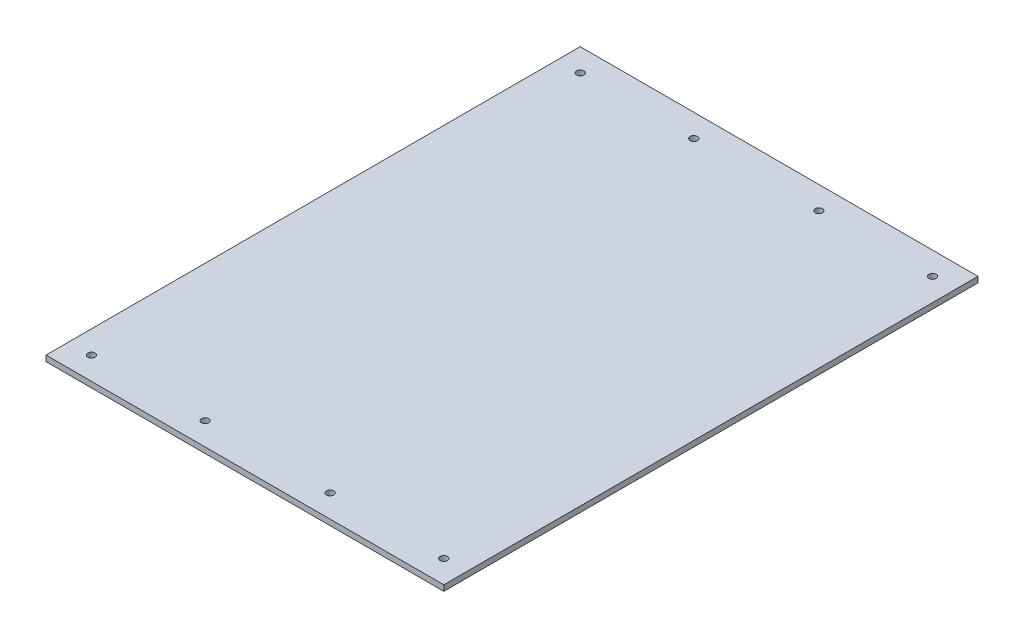
SolidWorks part; units mm, degrees
ref_plane "Front Plane" through (0, 0, 0) normal (0, 0, 1) x (1, 0, 0)
ref_plane "Top Plane" through (0, 0, 0) normal (0, 1, 0) x (1, 0, 0)
ref_plane "Right Plane" through (0, 0, 0) normal (1, 0, 0) x (0, 0, -1)
sketch "Sketch1" plane through (0, 0, 0) normal (0, 1, 0) x (1, 0, 0)
  line L1 (-175, -235) -> (175, -235)
  line L2 (-175, -235) -> (-175, 235)
  line L3 (-175, 235) -> (175, 235)
  line L4 (175, -235) -> (175, 235)
  line L5 (-175, -235) -> (175, 235) construction
  line L6 (-175, 235) -> (175, -235) construction
  point P0 (0, 0)
  dimension "D1" = 350
  dimension "D2" = 470
extrude "Boss-Extrude1" add sketch "Sketch1" along normal blind 5
hole_wizard "M6 Clearance Hole1" positions "Sketch3" profile "Sketch2" hole size "M6" standard "ANSI Metric"
sketch "Sketch3" plane through (0, 5, 0) normal (0, 1, 0) x (1, 0, 0)
  line L0 (-1089.4391, -215) -> (48910.5609, -215) construction
  line L1 (-1065.6521, 215) -> (48934.3479, 215) construction
  line L2 (-155, -977.1645) -> (-155, 49022.8355) construction
  line L3 (-55, -976.213) -> (-55, 49023.787) construction
  line L4 (55, -978.116) -> (55, 49021.884) construction
  line L5 (155, -979.0674) -> (155, 49020.9326) construction
  line L6 (-175, -235) -> (175, -235) construction
  line L7 (175, 235) -> (-175, 235) construction
  line L8 (-175, 235) -> (-175, -235) construction
  line L9 (175, -235) -> (175, 235) construction
  point P46 (-155, 215)
  point P47 (-55, 215)
  point P49 (55, 215)
  point P51 (155, 215)
  point P53 (-155, -215)
  point P55 (-55, -215)
  point P57 (55, -215)
  point P59 (155, -215)
  dimension "D1" = 20
  dimension "D2" = 20
  dimension "D3" = 20
  dimension "D4" = 20
  dimension "D5" = 100
  dimension "D6" = 100
sketch "Sketch2" plane through (-155, 5, -215) normal (1, 0, 0) x (0, 0, 1)
  line L0 (0, 0) -> (0, 11.9228)
  line L1 (0, 11.9228) -> (3.2, 10)
  line L2 (3.2, 10) -> (3.2, 0)
  line L5 (3.2, 0) -> (0, 0)
  line L10 (0, 11.9228) -> (-3.2, 10) construction
  line L11 (0, -6.35) -> (0, 107.95) construction
  dimension "Hole Dia." = 6.4
  dimension "Hole Depth" = 10
  dimension "Drill Angle" = 118
